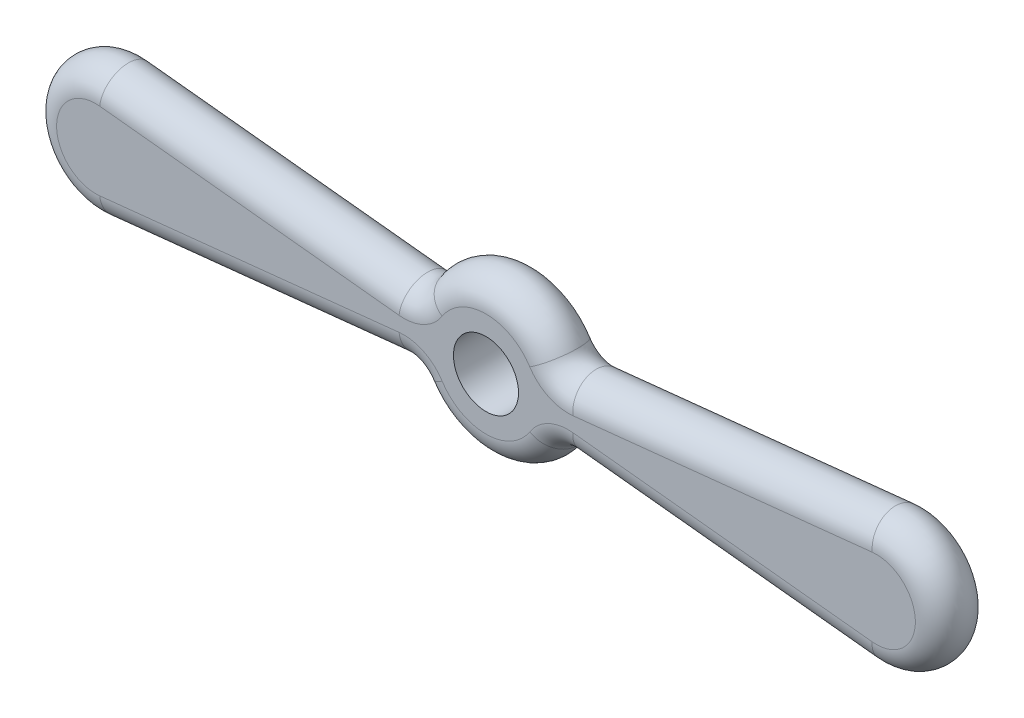
SolidWorks part; units mm, degrees
ref_plane "Front Plane" through (0, 0, 0) normal (0, 0, 1) x (1, 0, 0)
ref_plane "Top Plane" through (0, 0, 0) normal (0, 1, 0) x (1, 0, 0)
ref_plane "Right Plane" through (0, 0, 0) normal (1, 0, 0) x (0, 0, -1)
sketch "Sketch1" plane through (0, 0, 0) normal (0, 0, 1) x (1, 0, 0)
  line L0 (12.9432, 5.1092) -> (58.9547, 9.9452)
  line L1 (58.9547, -9.9452) -> (12.9432, -5.1092)
  line L2 (0, 0) -> (40.9321, 0) construction
  line L3 (0, 0) -> (0, 35.725) construction
  line L4 (-58.9547, -9.9452) -> (-12.9432, -5.1092)
  line L5 (-12.9432, 5.1092) -> (-58.9547, 9.9452)
  arc A0 (10.1037, 6.4742) -> (-10.1037, 6.4742) centre (0, 0) ccw
  circle A1 centre (0, 0) radius 5
  arc A2 (58.9547, 9.9452) -> (58.9547, -9.9452) centre (60, 0) cw
  arc A3 (12.9432, -5.1092) -> (10.1037, -6.4742) centre (12.6296, -8.0928) ccw
  arc A4 (12.9432, 5.1092) -> (10.1037, 6.4742) centre (12.6296, 8.0928) cw
  arc A5 (-12.9432, 5.1092) -> (-10.1037, 6.4742) centre (-12.6296, 8.0928) ccw
  arc A6 (-12.9432, -5.1092) -> (-10.1037, -6.4742) centre (-12.6296, -8.0928) cw
  arc A7 (-58.9547, 9.9452) -> (-58.9547, -9.9452) centre (-60, 0) ccw
  arc A8 (-10.1037, -6.4742) -> (10.1037, -6.4742) centre (0, 0) ccw
  dimension "D1" = 24
  dimension "D2" = 10
  dimension "D3" = 10
  dimension "D6" = 3
  dimension "D4" = 6
  dimension "D5" = 60
extrude "Boss-Extrude1" add sketch "Sketch1" along normal blind 8
fillet "Fillet1" 2 edges at (-35.949, 7.5272, 8) (-35.949, 7.5272, 0) type full round first side face at (0, 0, 8) second side face at (0, 0, 0) middle face at (-35.949, 7.5272, 4)
